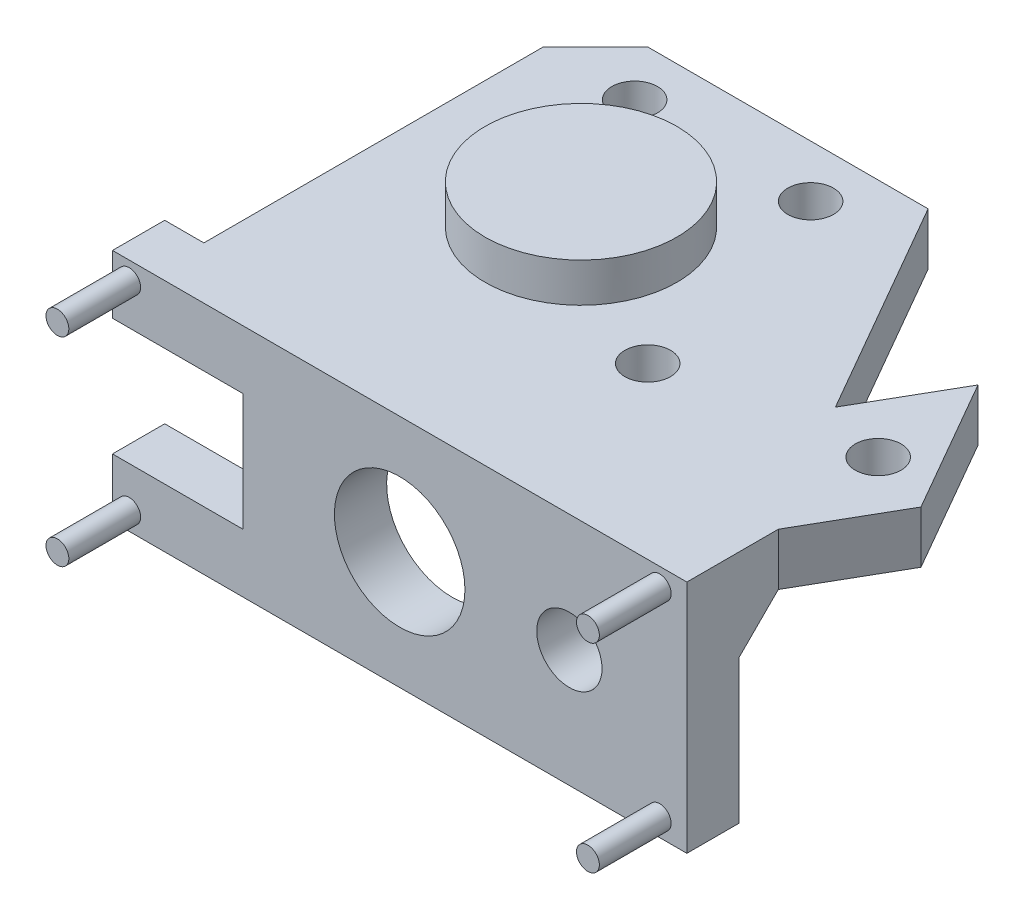
SolidWorks part; units mm, degrees
ref_plane "Спереди" through (0, 0, 0) normal (0, 0, 1) x (1, 0, 0)
ref_plane "Сверху" through (0, 0, 0) normal (0, 1, 0) x (1, 0, 0)
ref_plane "Справа" through (0, 0, 0) normal (1, 0, 0) x (0, 0, -1)
sketch "Эскиз1" plane through (0, 0, 0) normal (0, 0, 1) x (1, 0, 0)
  line L1 (-22, 9) -> (22, 9)
  line L2 (-22, 9) -> (-22, -9)
  line L3 (-22, -9) -> (22, -9)
  line L4 (22, 9) -> (22, -9)
  line L5 (-22, 9) -> (22, -9) construction
  line L6 (-22, -9) -> (22, 9) construction
  circle A0 centre (0, 0) radius 5
  point P0 (0, 0)
  dimension "D3" = 10
  dimension "D1" = 18
  dimension "D2" = 44
extrude "Бобышка-Вытянуть1" add sketch "Эскиз1" along normal blind 4
sketch "Эскиз2" plane through (0, 0, 4) normal (0, 0, 1) x (1, 0, 0)
  line L0 (-22, 0) -> (-17, 0)
  line L1 (-22, 9) -> (-22, -9) construction
  line L3 (-22, 4.5) -> (-12, 4.5)
  line L4 (-22, 4.5) -> (-22, -4.5)
  line L5 (-22, -4.5) -> (-12, -4.5)
  line L6 (-12, 4.5) -> (-12, -4.5)
  line L7 (-22, 4.5) -> (-12, -4.5) construction
  line L8 (-22, -4.5) -> (-12, 4.5) construction
  line M6 (-22, 9) -> (-22, -9)
  dimension "D1" = 5
  dimension "D2" = 10
  dimension "D3" = 9
extrude "Вырез-Вытянуть1" cut sketch "Эскиз2" against normal through all contours L6 L3 L5 M6 region at (-17, 4.3655, 4)
sketch "Эскиз3" plane through (0, 0, 4) normal (0, 0, 1) x (1, 0, 0)
  line L0 (-22, 9) -> (-22, 7.62)
  line L1 (-22, 9) -> (-22, 4.5) construction
  line L2 (-22, 7.62) -> (-20.72, 7.62)
  line L3 (-12, 0) -> (-22, 0)
  line L4 (-12, 4.5) -> (-12, -4.5) construction
  line L5 (-20.72, -7.62) -> (19.92, -7.62)
  circle A0 centre (-20.72, 7.62) radius 0.875
  circle A1 centre (-20.72, -7.62) radius 0.875
  circle A2 centre (19.92, -7.62) radius 0.875
  circle A3 centre (19.92, 7.62) radius 0.875
  dimension "D3" = 1.75
  dimension "D5" = 1.75
  dimension "D1" = 1.38
  dimension "D2" = 1.28
  dimension "D4" = 40.64
extrude "Бобышка-Вытянуть2" add sketch "Эскиз3" along normal blind 5.5 contours A0 | A1 | A2 | A3 region at (19.92, -6.7697, 4) region at (-21.5703, -7.62, 4) region at (-20.72, 6.7697, 4) region at (19.92, 7.62, 4)
sketch "Эскиз4" plane through (0, 0, 0) normal (0, 0, -1) x (-1, 0, 0)
  line L0 (22, 9) -> (19, 9)
  line L1 (-22, 9) -> (22, 9) construction
  line L2 (19, 9) -> (19, 4.5)
  line L3 (22, 4.5) -> (12, 4.5) construction
  line L4 (19, 9) -> (-22, 9)
  line L5 (-22, 9) -> (-22, 5)
  line L6 (-22, -9) -> (-22, 9) construction
  line L7 (-22, 5) -> (19, 5)
  line M7 (22, 9) -> (-22, 9)
  line M8 (-22, 9) -> (-22, -9)
  dimension "D1" = 3
  dimension "D2" = 4
extrude "Бобышка-Вытянуть3" add sketch "Эскиз4" along normal blind 30 contours L7 L2 M8 M7 region at (1.5, 7, 0)
sketch "Эскиз5" plane through (0, 9, 0) normal (0, 1, 0) x (1, 0, 0)
  line L0 (-19, 0) -> (-5.61, 0)
  line L1 (-5.61, 0) -> (-5.61, 15.5)
  circle A0 centre (-5.61, 15.5) radius 7.35
  dimension "D3" = 14.7
  dimension "D1" = 13.39
  dimension "D2" = 15.5
extrude "Бобышка-Вытянуть4" add sketch "Эскиз5" along normal blind 3 contours A0 region at (-0.5598, 9, -10.4498)
sketch "Эскиз6" plane through (0, 5, 0) normal (0, -1, 0) x (1, 0, 0)
  line L0 (-19, -30) -> (6.48, -30)
  line L1 (22, -30) -> (-19, -30) construction
  line L2 (22, 0) -> (22, -3.01)
  line L3 (22, -30) -> (22, 0) construction
  line L4 (6.48, -30) -> (22, -3.01)
  line L5 (22, -30) -> (6.48, -30)
  line M5 (-19, -30) -> (22, -30)
  line M6 (22, -30) -> (22, 0)
  dimension "D1" = 25.48
  dimension "D2" = 3.01
extrude "Вырез-Вытянуть2" cut sketch "Эскиз6" against normal through all contours L4 M5 M6 region at (16.8267, 5, -21.0033)
sketch "Эскиз7" plane through (0, 5, 0) normal (0, -1, 0) x (1, 0, 0)
  line L0 (22, -3.01) -> (16.0879, -13.2914)
  line L1 (6.48, -30) -> (22, -3.01) construction
  line L2 (22, -3.01) -> (25.9879, -9.9452)
  line L3 (20.0758, -20.2266) -> (25.9879, -9.9452)
  line L4 (20.0758, -20.2266) -> (16.0879, -13.2914)
  line L5 (6.48, -30) -> (16.0879, -30)
  line L6 (16.0879, -30) -> (16.0879, -13.2914)
  line L7 (6.48, -30) -> (16.0879, -13.2914)
  line L8 (25.6958, -30) -> (16.0879, -13.2914)
  line M3 (6.48, -30) -> (22, -3.01)
  dimension "D1" = 11.86
  dimension "D2" = 8
extrude "Бобышка-Вытянуть6" add sketch "Эскиз7" against normal blind 4 contours L4 L3 L2 M3 region at (21.0379, 5, -11.6183)
sketch "Эскиз8" plane through (0, 5, 0) normal (0, -1, 0) x (1, 0, 0)
  line L0 (23.0319, -15.0859) -> (21.0379, -11.6183)
  line L1 (20.0758, -20.2266) -> (25.9879, -9.9452) construction
  line L2 (20.0758, -20.2266) -> (16.0879, -13.2914) construction
  line L3 (-19, -30) -> (-19, -26)
  line L4 (-19, -30) -> (-19, 0) construction
  line L5 (-19, -26) -> (-12, -26)
  line L6 (6.48, -30) -> (6.48, -26)
  line L7 (6.48, -26) -> (1.48, -26)
  line L8 (-19, 0) -> (-19, -9)
  line L9 (-19, -9) -> (6, -9)
  circle A0 centre (21.0379, -11.6183) radius 1.75
  circle A1 centre (-12, -26) radius 1.75
  circle A2 centre (1.48, -26) radius 1.75
  circle A3 centre (6, -9) radius 1.75
  dimension "D2" = 3.5
  dimension "D1" = 4
  dimension "D3" = 4
  dimension "D4" = 5
  dimension "D5" = 7
  dimension "D6" = 9
  dimension "D7" = 25
extrude "Вырез-Вытянуть3" cut sketch "Эскиз8" against normal through all contours A3 | A0 | A2 | A1 region at (22.5099, 5, -12.4698) region at (-12, 5, -27.7005) region at (-0.2205, 5, -26) region at (6, 5, -10.7005)
chamfer "Фаска1" distance 3 angle 45 2 edges at (-9.5, 5, 0)
sketch "Эскиз9" plane through (0, 0, 4) normal (0, 0, 1) x (1, 0, 0)
  line L0 (0, 0) -> (13, 0)
  circle A0 centre (13, 0) radius 2.5
  dimension "D1" = 5
  dimension "D2" = 13
extrude "Вырез-Вытянуть5" cut sketch "Эскиз9" against normal through all contours A0 region at (13, -2.4293, 4)
chamfer "Фаска2" distance 4 angle 45 1 edges at (-19, 7, -30)
